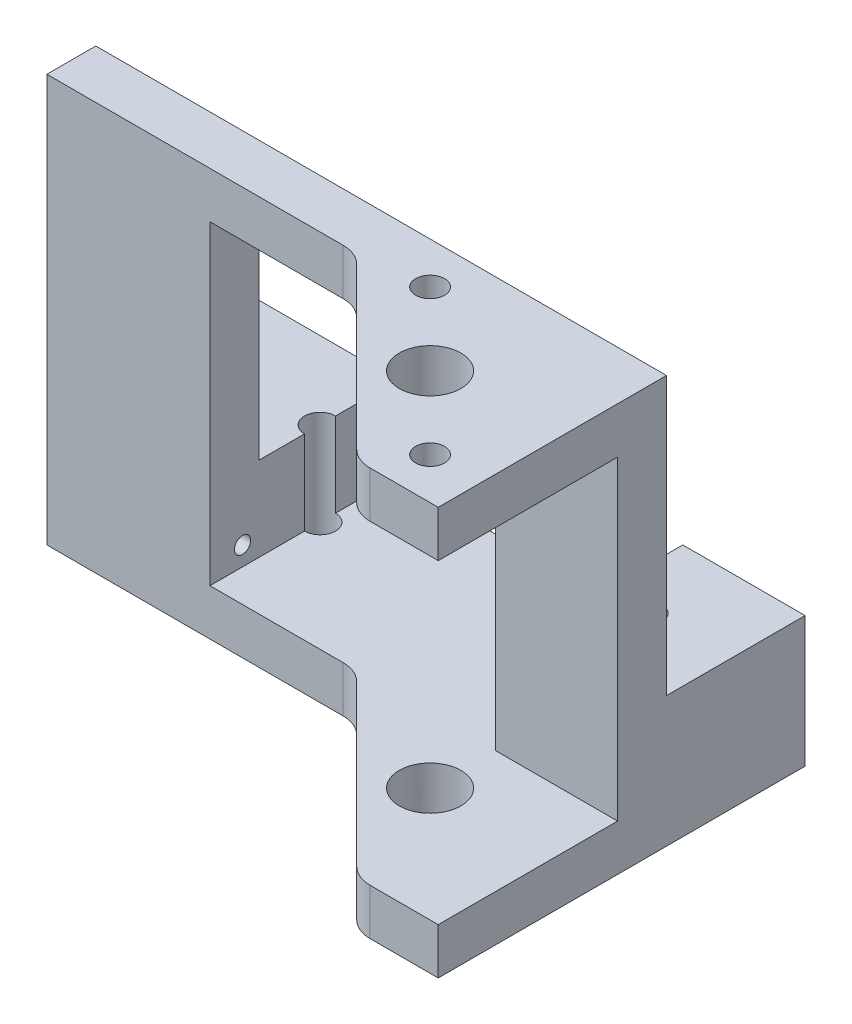
SolidWorks part; units mm, degrees
ref_plane "Front Plane" through (0, 0, 0) normal (0, 0, 1) x (1, 0, 0)
ref_plane "Top Plane" through (0, 0, 0) normal (0, 1, 0) x (1, 0, 0)
ref_plane "Right Plane" through (0, 0, 0) normal (1, 0, 0) x (0, 0, -1)
sketch "Sketch1" plane through (0, 0, 0) normal (0, 0, 1) x (1, 0, 0)
  line L1 (50.8, -31.75) -> (-50.8, -31.75)
  line L2 (50.8, -31.75) -> (50.8, 31.75)
  line L3 (50.8, 31.75) -> (-50.8, 31.75)
  line L4 (-50.8, -31.75) -> (-50.8, 31.75)
  line L5 (50.8, -31.75) -> (-50.8, 31.75) construction
  line L6 (50.8, 31.75) -> (-50.8, -31.75) construction
  point P0 (0, 0)
  dimension "D1" = 63.5
  dimension "D2" = 101.6
extrude "Boss-Extrude1" add sketch "Sketch1" along normal blind 57.15
sketch "Sketch2" plane through (0, 0, 57.15) normal (0, 0, 1) x (1, 0, 0)
  line L0 (-50.8, 31.75) -> (-50.8, -31.75) construction
  line L1 (50.8, -24.55) -> (-50.8, -24.55)
  line L2 (50.8, -24.55) -> (50.8, 24.55)
  line L3 (50.8, 24.55) -> (-50.8, 24.55)
  line L4 (-50.8, -24.55) -> (-50.8, 24.55)
  line L5 (50.8, -24.55) -> (-50.8, 24.55) construction
  line L6 (50.8, 24.55) -> (-50.8, -24.55) construction
  line L7 (50.8, 31.75) -> (-50.8, 31.75) construction
  point P0 (0, 0)
  dimension "D1" = 7.2
extrude "Cut-Extrude2" cut sketch "Sketch2" against normal blind 27.94
sketch "Sketch3" plane through (0, 0, 0) normal (0, 0, -1) x (-1, 0, 0)
  line L0 (-50.8, -31.75) -> (-50.8, 31.75) construction
  line L1 (50.8, 31.75) -> (-50.8, 31.75)
  line L2 (50.8, 31.75) -> (50.8, -11.43)
  line L3 (50.8, -11.43) -> (-50.8, -11.43)
  line L4 (-50.8, 31.75) -> (-50.8, -11.43)
  dimension "D1" = 43.18
extrude "Cut-Extrude3" cut sketch "Sketch3" against normal blind 21.59
sketch "Sketch5" plane through (0, -31.75, 0) normal (0, -1, 0) x (1, 0, 0)
  line L0 (-12.7, 12.06) -> (38.1, 12.06) construction
  line L1 (50.8, 21.59) -> (-50.8, 21.59) construction
  line L2 (50.8, 57.15) -> (50.8, 0) construction
  circle A0 centre (-12.7, 12.06) radius 2.415
  circle A1 centre (38.1, 12.06) radius 2.415
  dimension "D3" = 4.83
  dimension "D4" = 12.7
  dimension "D1" = 9.53
  dimension "D2" = 50.8
extrude "Cut-Extrude4" cut sketch "Sketch5" against normal blind 25.4
sketch "Sketch6" plane through (0, 0, 21.59) normal (0, 0, -1) x (-1, 0, 0)
  line L0 (-40.515, -11.43) -> (15.115, -11.43) construction
  line L1 (-40.515, -11.43) -> (-40.515, -31.75) construction
  line L2 (15.115, -31.75) -> (15.115, -11.43) construction
  line L3 (-50.8, -11.43) -> (50.8, -11.43) construction
  line L5 (-248.92, 7.62) -> (260.35, 7.62) construction
  circle A1 centre (-5.08, 2.286) radius 2.2225
  dimension "D2" = 5.08
  dimension "D3" = 4.445
  dimension "D1" = 5.334
extrude "Cut-Extrude5" cut sketch "Sketch6" against normal blind 5.08
sketch "Sketch7" plane through (0, -31.75, 0) normal (0, -1, 0) x (1, 0, 0)
  line L0 (50.8, 57.15) -> (50.8, 0) construction
  line L2 (-50.8, 29.21) -> (50.8, 29.21) construction
  circle A0 centre (31.75, 39.37) radius 4.8
  dimension "D1" = 9.6
  dimension "D2" = 19.05
  dimension "D3" = 10.16
extrude "Cut-Extrude6" cut sketch "Sketch7" against normal up to surface (63.5 mm away) up to face at (0, 31.75, 39.37)
sketch "Sketch8" plane through (0, 31.75, 0) normal (0, 1, 0) x (1, 0, 0)
  line L0 (20.4363, -28.0563) -> (43.0637, -50.6837) construction
  line L1 (50.8, -29.21) -> (-50.8, -29.21) construction
  circle A0 centre (31.75, -39.37) radius 16 construction
  circle A1 centre (20.4363, -28.0563) radius 2.25
  circle A2 centre (43.0637, -50.6837) radius 2.25
  dimension "D1" = 32
  dimension "D2" = 4.5
  dimension "D3" = 45
sketch "Sketch9" plane through (0, 0, 29.21) normal (0, 0, 1) x (1, 0, 0)
  line L0 (50.8, 31.75) -> (-50.8, 31.75) construction
  line L5 (50.8, 24.55) -> (-50.8, 24.55) construction
  line L6 (-12.7, 24.55) -> (31.75, 24.55)
  line L7 (-12.7, 24.55) -> (-12.7, -24.55)
  line L8 (-12.7, -24.55) -> (31.75, -24.55)
  line L9 (31.75, 24.55) -> (31.75, -24.55)
  line L10 (-50.8, -24.55) -> (50.8, -24.55) construction
  line L11 (-50.8, 24.55) -> (-50.8, -24.55) construction
  line L12 (50.8, -24.55) -> (50.8, 24.55) construction
  line L13 (-50.8, -31.75) -> (-38.1, -31.75)
  line L14 (-50.8, -31.75) -> (-50.8, 31.75)
  line L15 (-50.8, 31.75) -> (-38.1, 31.75)
  line L16 (-38.1, -31.75) -> (-38.1, 31.75)
  line L17 (-50.8, -31.75) -> (-38.1, 31.75) construction
  line L18 (-50.8, 31.75) -> (-38.1, -31.75) construction
  line L19 (-50.8, -31.75) -> (50.8, -31.75) construction
  point P5 (-44.45, 0)
  dimension "D1" = 19.05
  dimension "25in" = 38.1
  dimension "D2" = 12.7
extrude "Cut-Extrude7" cut sketch "Sketch9" against normal through all both and the other way through all
extrude "Cut-Extrude8" cut sketch "Sketch8" against normal up to next
sketch "Sketch10" [suppressed] plane through (0, 0, 29.21) normal (0, 0, 1) x (1, 0, 0)
  line L1 (-30.607, -1.778) -> (-30.607, -6.604) construction
  circle A0 centre (-33.2489, -4.191) radius 2.286
  point P5 (-30.607, -4.191)
  dimension "D1" = 4.572
sketch "Sketch11" [suppressed] plane through (0, 0, 21.59) normal (0, 0, -1) x (-1, 0, 0)
  circle A0 centre (33.2489, -4.191) radius 2.286
  dimension "D1" = 4.572
extrude "Cut-Extrude9" [suppressed] cut sketch "Sketch11" against normal blind 3.81
sketch "Sketch12" plane through (-12.7, 0, 0) normal (1, 0, 0) x (0, 0, -1)
  line L0 (-29.21, -24.55) -> (-29.21, 24.55) construction
  line L1 (-24.13, -21.59) -> (-24.13, 21.59) construction
  line L2 (-21.59, 24.55) -> (-21.59, -11.43) construction
  circle A0 centre (-24.13, -21.59) radius 1.27
  circle A1 centre (-24.13, 21.59) radius 1.27
  point P0 (-29.21, 0)
  point P8 (-24.13, 0)
  point P10 (0, 0)
  dimension "D1" = 2.54
  dimension "D2" = 2.54
  dimension "D3" = 43.18
extrude "Cut-Extrude10" cut sketch "Sketch12" against normal up to surface (25.4 mm away) up to face at (-38.1, -2.286, 33.02)
sketch "Sketch13" plane through (0, 31.75, 0) normal (0, 1, 0) x (1, 0, 0)
  line L0 (-38.1, -29.21) -> (10.16, -29.21)
  line L1 (10.16, -29.21) -> (38.1, -57.15)
  line L2 (50.8, -57.15) -> (-38.1, -57.15) construction
  line L3 (43.0637, -50.6837) -> (20.4363, -28.0563) construction
  line L4 (-38.1, -29.21) -> (-38.1, -57.15)
  line L5 (-38.1, -57.15) -> (38.1, -57.15)
  line L6 (-38.1, -21.59) -> (-38.1, -57.15) construction
extrude "Cut-Extrude12" cut sketch "Sketch13" against normal through all
fillet "Fillet1" radius 5.08 4 edges at (38.1, -28.15, 57.15) (38.1, 28.15, 57.15) (10.16, 28.15, 29.21) (10.16, -28.15, 29.21)
